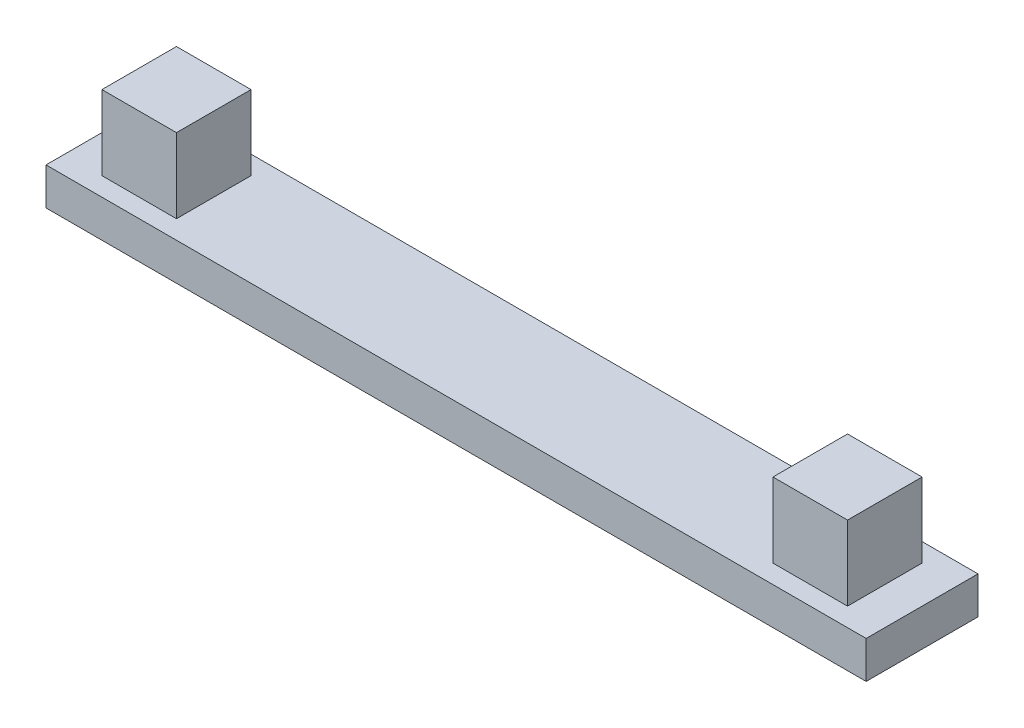
SolidWorks part; units mm, degrees
ref_plane "Front Plane" through (0, 0, 0) normal (0, 0, 1) x (1, 0, 0)
ref_plane "Top Plane" through (0, 0, 0) normal (0, 1, 0) x (1, 0, 0)
ref_plane "Right Plane" through (0, 0, 0) normal (1, 0, 0) x (0, 0, -1)
sketch "Sketch1" plane through (0, 0, 0) normal (0, 1, 0) x (1, 0, 0)
  line L1 (0, 0) -> (22, 0)
  line L2 (0, 0) -> (0, 3)
  line L3 (0, 3) -> (22, 3)
  line L4 (22, 0) -> (22, 3)
  line L5 (0, 0) -> (22, 3) construction
  line L6 (0, 3) -> (22, 0) construction
  line L7 (1, 2.5) -> (3, 2.5)
  line L8 (1, 2.5) -> (1, 0.5)
  line L9 (1, 0.5) -> (3, 0.5)
  line L10 (3, 2.5) -> (3, 0.5)
  line L11 (1, 2.5) -> (3, 0.5) construction
  line L12 (1, 0.5) -> (3, 2.5) construction
  line L13 (19, 2.5) -> (21, 2.5)
  line L14 (19, 2.5) -> (19, 0.5)
  line L15 (19, 0.5) -> (21, 0.5)
  line L16 (21, 2.5) -> (21, 0.5)
  line L17 (19, 2.5) -> (21, 0.5) construction
  line L18 (19, 0.5) -> (21, 2.5) construction
  point P4 (11, 1.5)
  point P10 (2, 1.5)
  point P15 (20, 1.5)
  point P17 (0, 1.5)
  point P22 (22, 1.5)
  dimension "D1" = 22
  dimension "D2" = 3
  dimension "D3" = 18
  dimension "D4" = 2
  dimension "D5" = 9
extrude "Boss-Extrude1" add sketch "Sketch1" along normal blind 1 contours L1 L4 L3 L2 L7 L10 L9 L8 L13 L16 L15 L14 region at (11, 0, -1.5)
ref_plane "Plane1" through (3, 0, -2.5) normal (1, 0, 0) x (0, 0, -1)
extrude "Boss-Extrude2" add sketch "Sketch1<3>" along normal blind 3 contours L7 L10 L9 L8 | L13 L16 L15 L14
sketch "Sketch1<3>" plane through (0, 0, 0) normal (0, 1, 0) x (1, 0, 0) same geometry as "Sketch1"
